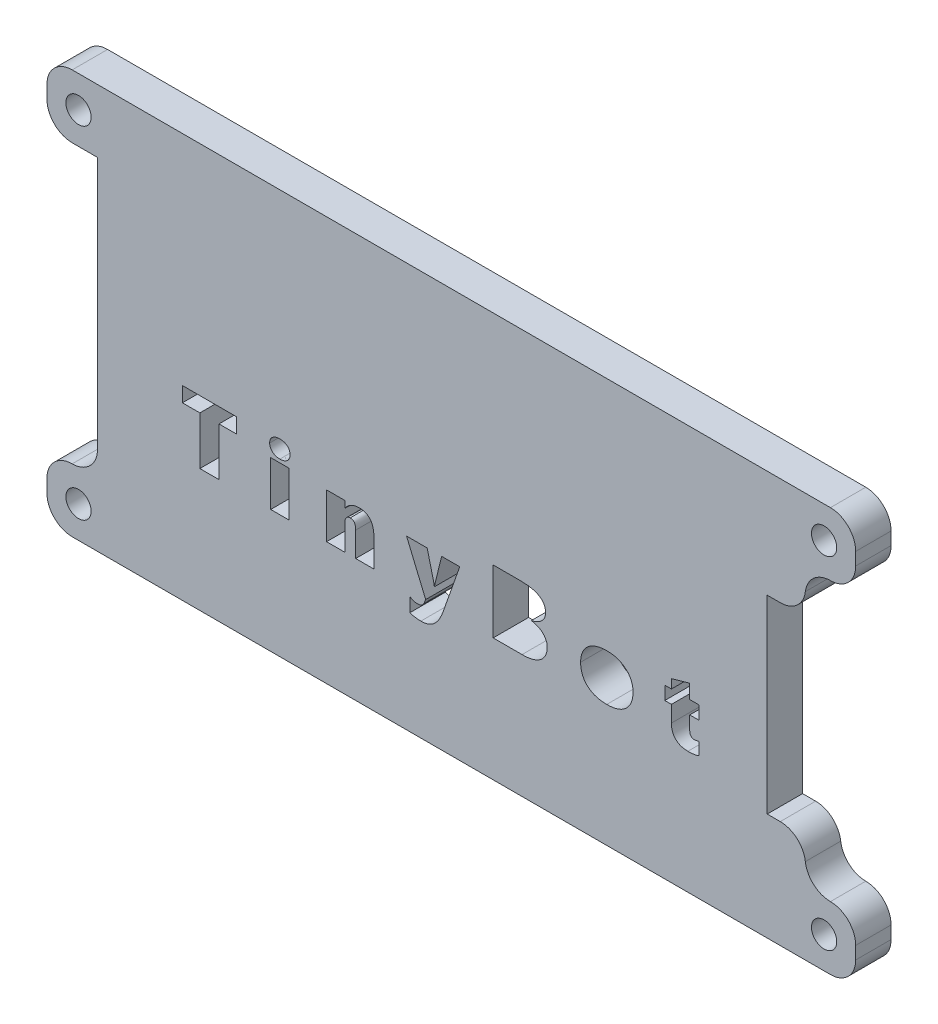
SolidWorks part; units mm, degrees
ref_plane "Front Plane" through (0, 0, 0) normal (0, 0, 1) x (1, 0, 0)
ref_plane "Top Plane" through (0, 0, 0) normal (0, 1, 0) x (1, 0, 0)
ref_plane "Right Plane" through (0, 0, 0) normal (1, 0, 0) x (0, 0, -1)
sketch "Sketch1" plane through (0, 0, 0) normal (0, 0, 1) x (1, 0, 0)
  line L1 (-28, -16) -> (28, -16)
  line L2 (-28, -16) -> (-28, 16)
  line L3 (-28, 16) -> (28, 16)
  line L4 (28, -16) -> (28, 16)
  line L5 (-28, -16) -> (28, 16) construction
  line L6 (-28, 16) -> (28, -16) construction
  point P0 (0, 0)
  dimension "D1" = 56
  dimension "D2" = 32
extrude "Boss-Extrude1" add sketch "Sketch1" along normal blind 2.8
sketch "Sketch2" plane through (0, 0, 2.8) normal (0, 0, 1) x (1, 0, 0)
  line L0 (28, -16) -> (28, 16) construction
  line L1 (28, 7.5) -> (25, 7.5)
  line L2 (28, 7.5) -> (28, -7.5)
  line L3 (28, -7.5) -> (25, -7.5)
  line L4 (25, 7.5) -> (25, -7.5)
  dimension "D1" = 3
  dimension "D2" = 15
  dimension "D3" = 7.5
extrude "Cut-Extrude1" cut sketch "Sketch2" against normal through all
sketch "Sketch3" plane through (0, 0, 0) normal (0, 0, 1) x (1, 0, 0)
  line L0 (-28, 0) -> (0, 0) construction
  line L1 (-28, 16) -> (-32, 16)
  line L2 (-28, 16) -> (-28, 11)
  line L3 (-28, 11) -> (-32, 11)
  line L4 (-32, 16) -> (-32, 11)
  line L5 (-28, 16) -> (-28, -16) construction
  line L6 (0, 0) -> (0, 16) construction
  line L7 (28, 16) -> (-28, 16) construction
  line L8 (28, 11) -> (32, 11)
  line L9 (32, 16) -> (32, 11)
  line L10 (28, 16) -> (32, 16)
  line L11 (28, 16) -> (28, 11)
  line L12 (28, -16) -> (28, -11)
  line L13 (28, -16) -> (32, -16)
  line L14 (32, -16) -> (32, -11)
  line L15 (28, -11) -> (32, -11)
  line L16 (-28, -11) -> (-32, -11)
  line L17 (-32, -16) -> (-32, -11)
  line L18 (-28, -16) -> (-32, -16)
  line L19 (-28, -16) -> (-28, -11)
  dimension "D1" = 4
  dimension "D2" = 5
extrude "Boss-Extrude2" add sketch "Sketch3" along normal blind 2.8
sketch "Sketch4" plane through (0, 0, 2.8) normal (0, 0, 1) x (1, 0, 0)
  line L0 (-32, 13.5) -> (32, 13.5) construction
  line L1 (-32, 16) -> (-32, 11) construction
  line L2 (32, 11) -> (32, 16) construction
  line L3 (0, 13.5) -> (0, 0) construction
  line L4 (0, 0) -> (-28, 0) construction
  line L5 (-28, 11) -> (-28, -11) construction
  circle A0 centre (-29.5, 13.5) radius 1
  circle A1 centre (29.5, 13.5) radius 1
  circle A2 centre (29.5, -13.5) radius 1
  circle A3 centre (-29.5, -13.5) radius 1
  dimension "D1" = 2
  dimension "D2" = 2.5
extrude "Cut-Extrude2" cut sketch "Sketch4" against normal through all
fillet "Fillet1" radius 2 11 edges at (32, 16, 1.4) (32, 11, 1.4) (28, 11, 1.4) (28, -11, 1.4) (32, -11, 1.4) (32, -16, 1.4) (-32, -16, 1.4) (-28, -11, 1.4) (-32, -11, 1.4) (-32, 16, 1.4) (-32, 11, 1.4)
fillet "Fillet2" radius 2 2 edges at (28, -7.5, 1.4) (28, 7.5, 1.4)
sketch "Sketch5" plane through (0, 0, 2.8) normal (0, 0, 1) x (1, 0, 0)
  text T0 "TinyBot" font "Segoe UI Black" height 5
extrude "Cut-Extrude3" cut sketch "Sketch5" against normal through all body kept at (28.0157, 9.25, 0)
